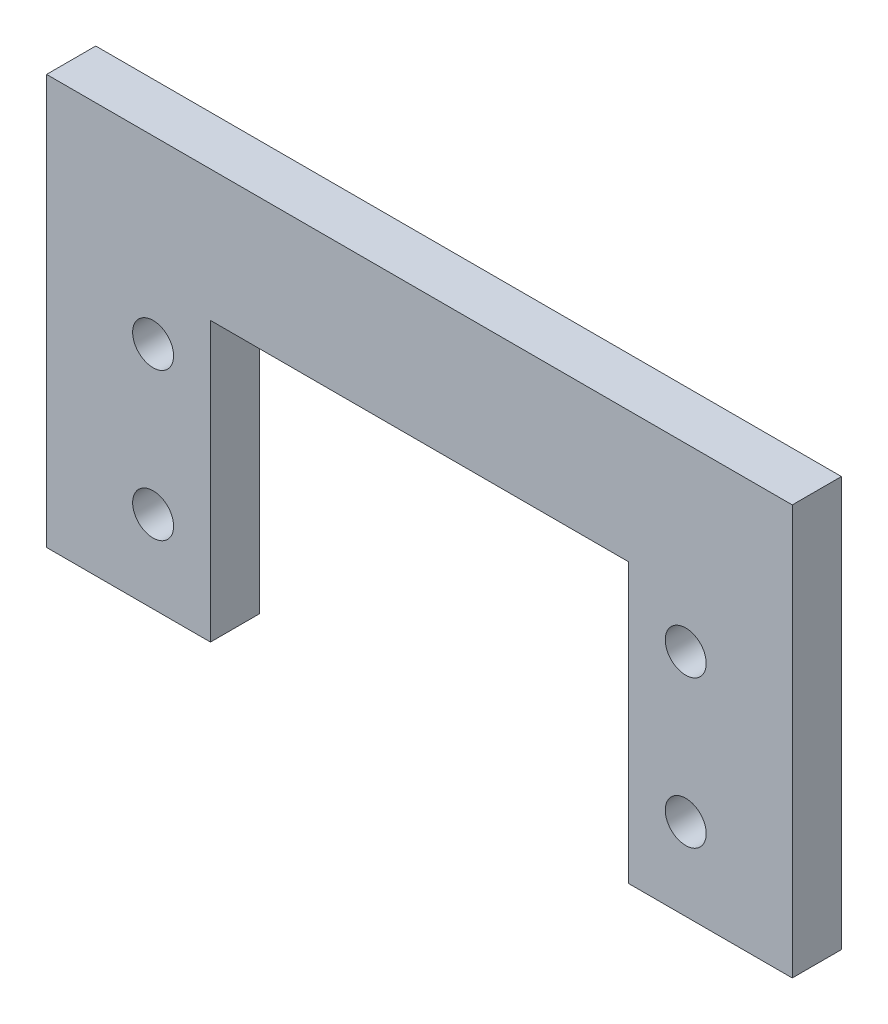
SolidWorks part; units mm, degrees
ref_plane "Front Plane" through (0, 0, 0) normal (0, 0, 1) x (1, 0, 0)
ref_plane "Top Plane" through (0, 0, 0) normal (0, 1, 0) x (1, 0, 0)
ref_plane "Right Plane" through (0, 0, 0) normal (1, 0, 0) x (0, 0, -1)
sketch "Sketch1" plane through (0, 0, 0) normal (0, 0, 1) x (1, 0, 0)
  line L0 (0, -55) -> (0, 55) construction
  line L1 (-12.25, 0) -> (12.25, 0)
  line L2 (-12.25, 0) -> (-12.25, -20.5928)
  line L3 (-12.25, -20.5928) -> (12.25, -20.5928)
  line L4 (12.25, 0) -> (12.25, -20.5928)
  line L5 (-22.75, 9) -> (-12.75, 9)
  line L6 (-22.75, 9) -> (-22.75, -16)
  line L7 (-22.75, -16) -> (-12.75, -16)
  line L8 (-12.75, 1) -> (-12.75, -16)
  line L9 (22.75, -16) -> (12.75, -16)
  line L10 (12.75, 1) -> (12.75, -16)
  line L11 (22.75, 9) -> (12.75, 9)
  line L12 (22.75, 9) -> (22.75, -16)
  line L13 (-12.75, 9) -> (12.75, 9)
  line L14 (12.75, 1) -> (-12.75, 1)
  circle A0 centre (-16.25, -2) radius 1.25
  circle A1 centre (-16.25, -11) radius 1.25
  circle A2 centre (16.25, -11) radius 1.25
  circle A3 centre (16.25, -2) radius 1.25
  point P8 (0, 0)
  dimension "D5" = 2.5
  dimension "D8" = 2.5
  dimension "D1" = 24.5
  dimension "D2" = 10
  dimension "D3" = 0.5
  dimension "D4" = 25
  dimension "D6" = 4
  dimension "D7" = 2
  dimension "D9" = 9
  dimension "D10" = 4
  dimension "D11" = 5
  dimension "D12" = 1
extrude "Boss-Extrude1" add sketch "Sketch1" along normal blind 3 contours L5 L13 L11 L12 L9 L10 L14 L8 L7 L6
extrude "Cut-Extrude1" cut sketch "Sketch1<3>" along normal blind 3 contours A1 | A3 | A2 | A0 region at (-16.25, -11, 0) region at (16.25, -11, 0) region at (16.25, -2, 0)
sketch "Sketch1<3>" plane through (0, 0, 0) normal (0, 0, 1) x (1, 0, 0) same geometry as "Sketch1"
